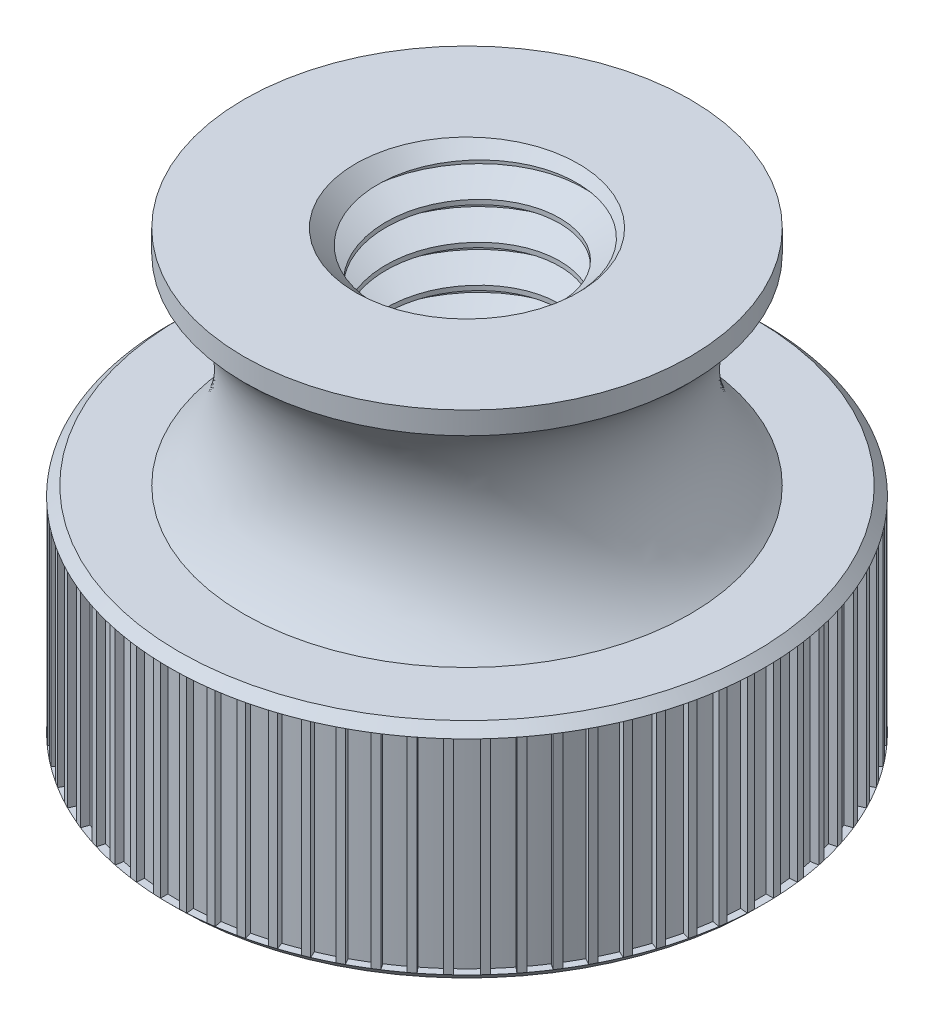
SolidWorks part; units mm, degrees
material "AISI 304"
ref_plane "Front Plane" through (0, 0, 0) normal (0, 0, 1) x (1, 0, 0)
ref_plane "Top Plane" through (0, 0, 0) normal (0, 1, 0) x (1, 0, 0)
ref_plane "Right Plane" through (0, 0, 0) normal (1, 0, 0) x (0, 0, -1)
sketch "Sketch1" plane through (0, 0, 0) normal (0, 0, 1) x (1, 0, 0)
  line L0 (0, 0) -> (0, 6) construction
  line L1 (0, 6) -> (-3, 6)
  line L2 (-4, 3) -> (-4, 0)
  line L3 (-4, 0) -> (0, 0)
  line L4 (0, 0) -> (0, 6)
  line L5 (0, 0) -> (0, -2.6189) construction
  line L6 (-2.4, 3) -> (-2.4, 6) construction
  line L7 (-4, 3) -> (-3, 3)
  line L10 (-3, 6) -> (-3, 5.7)
  arc A0 (-3, 3) -> (-3, 5.7) centre (-4.2188, 4.35) ccw
  point P1 (0, 3)
  dimension "D1" = 0.3
  dimension "A" = 8
  dimension "D2" = 0.6
  dimension "B" = 6
  dimension "C" = 6
  dimension "D" = 3
revolve "Revolve1" add sketch "Sketch1" angle 360 about L0
sketch "Sketch3" plane through (0, 0, 0) normal (0, 1, 0) x (1, 0, 0)
  circle A0 centre (0, 0) radius 1.5
  dimension "OD" = 3
extrude "Cut-Extrude1" cut sketch "Sketch3" along normal through all
sketch "Sketch4" plane through (0, 0, 0) normal (0, 1, 0) x (1, 0, 0)
  circle A1 centre (0, 0) radius 1.5
  circle A2 centre (0, 0) radius 1.5
  dimension "D1" = 0
curve "Helix/Spiral1" pitch 0.5 height 9 turns 18 parameters "pitch"=0.5
sketch "Sketch21" plane through (0, 0, 0) normal (0, 1, 0) x (1, 0, 0)
  line L0 (0, 1.5) -> (0, 4)
  circle A0 centre (0, 0) radius 4 construction
  circle A1 centre (0, 0) radius 1.5 construction
  circle A2 centre (0, 0) radius 4 construction
  circle A3 centre (0, 0) radius 1.5 construction
  dimension "D1" = 2.5
sketch "Sketch5" plane through (0, 0, 0) normal (1, 0, 0) x (0, 0, -1)
  line L0 (-1.5, 0) -> (-1.5, -0.4375)
  line L1 (-1.5, -0.4375) -> (-1.1752, -0.25)
  line L2 (-1.1752, -0.25) -> (-1.1752, -0.1875)
  line L3 (-1.1752, -0.1875) -> (-1.5, 0)
  line L4 (-1.1752, -0.2187) -> (-1.5, -0.2187) construction
  line L5 (-1.3376, -0.3437) -> (-1.3376, -0.0937) construction
  line L6 (1.5, 0) -> (-1.5, 0) construction
  dimension "D1" = 0.0625
  dimension "D2" = 0.25
  dimension "D3" = 60
sweep "Sweep1" add profiles "Sketch5" path "Helix/Spiral1"
sketch "Sketch13" plane through (0, 0, 0) normal (0, -1, 0) x (1, 0, 0)
  circle A1 centre (0, 0) radius 4
  circle A2 centre (0, 0) radius 4
  dimension "D1" = 0
extrude "Cut-Extrude2" cut sketch "Sketch13" along normal through all
sketch "Sketch14" plane through (0, 6, 0) normal (0, 1, 0) x (1, 0, 0)
  circle A0 centre (0, 0) radius 4 construction
  circle A1 centre (0, 0) radius 4
extrude "Cut-Extrude3" cut sketch "Sketch14" along normal through all
sketch "Sketch15" plane through (0, 0, 0) normal (0, -1, 0) x (1, 0, 0)
  circle A0 centre (0, 0) radius 1.5 construction
  circle A1 centre (0, 0) radius 1.5
extrude "Cut-Extrude4" cut sketch "Sketch15" against normal through all draft 45
sketch "Sketch16" plane through (0, 6, 0) normal (0, 1, 0) x (1, 0, 0)
  circle A0 centre (0, 0) radius 1.5 construction
  circle A1 centre (0, 0) radius 1.5
extrude "Cut-Extrude5" cut sketch "Sketch16" against normal through all draft 45
chamfer "Chamfer1" distance 0.125 angle 45 2 edges at (0, 3, -4) (0, 0, -4)
sketch "Sketch11" plane through (0, 0, 0) normal (0, 0, 1) x (1, 0, 0)
  line L0 (-1.5, 6) -> (-1.5, 0)
  line L1 (1.5, 6) -> (1.5, 0)
  line L2 (3, 6) -> (-3, 6) construction
  line L4 (-1.5, 0) -> (1.5, 0) construction
  dimension "D1" = 3
sketch "Sketch12" plane through (0, 0, 0) normal (1, 0, 0) x (0, 0, -1)
  line L0 (-1.5, 6) -> (-1.5, 0)
  line L1 (1.5, 6) -> (1.5, 0)
  line L2 (-1.5, 0) -> (1.5, 0) construction
  line L3 (3, 6) -> (-3, 6) construction
  line L5 (-3.875, 0) -> (3.875, 0) construction
  dimension "D1" = 3
ref_plane "Plane1" through (0, 0, -12.7) normal (0, 0, 1) x (1, 0, 0)
sketch "Sketch17" plane through (0, 0, -12.7) normal (0, 0, 1) x (1, 0, 0)
  line L0 (-0.127, 0.125) -> (-0.127, 2.875)
  line L1 (4, 0.125) -> (-4, 0.125) construction
  line L2 (4, 2.875) -> (-4, 2.875) construction
  line L3 (0.127, 0.125) -> (0.127, 2.875)
  line L4 (0, 0.125) -> (0, 2.875) construction
  line L5 (-0.127, 0.125) -> (0.127, 0.125)
  line L6 (-0.127, 2.875) -> (0.127, 2.875)
  line L7 (0, 1.5) -> (6.048, 1.5) construction
  line L8 (0, 1.5) -> (0, 0) construction
  dimension "D1" = 0
  dimension "D2" = 0.254
extrude "Cut-Extrude6" cut sketch "Sketch17" along normal offset from surface (8.802 mm away) 0.1
pattern_circular "CirPattern1" count 72 over 360 about axis through (0, 0, 0) along (0, 1, 0) of "Cut-Extrude6"
sketch "Sketch18" plane through (0, 6, 0) normal (0, 1, 0) x (1, 0, 0)
  circle A0 centre (0, 0) radius 4
  arc A2 (1.1574, 3.8289) -> (0.9121, 3.8946) centre (0, 0) ccw construction
ref_plane "Plane3" through (0, 3, 0) normal (0, 1, 0) x (-1, 0, 0)
equation "\"D1@Sketch5\" = \"pitch@Helix/Spiral1\"*.125"
equation "\"D2@Sketch5\" = \"pitch@Helix/Spiral1\"*.5"
equation "\"D1@Sketch11\" = \"OD@Sketch3\""
equation "\"D1@Sketch12\" = \"OD@Sketch3\""
equation "\"D1@Chamfer1\" = \"pitch@Helix/Spiral1\"*.25"
equation "\"D3@Helix/Spiral1\" = \"B@Sketch1\"+3"
equation "\"D1@Sketch1\" = \"D@Sketch1\"/10"
equation "\"D2@Sketch1\" = \"C@Sketch1\"*.1"
